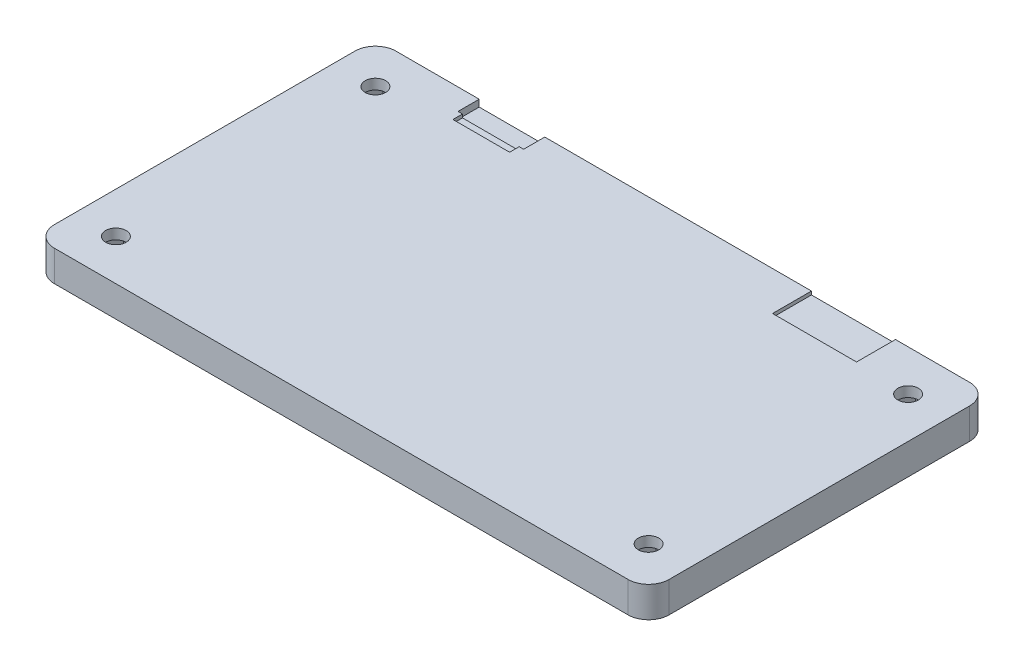
SolidWorks part; units mm, degrees
ref_plane "前视基准面" through (0, 0, 0) normal (0, 0, 1) x (1, 0, 0)
ref_plane "上视基准面" through (0, 0, 0) normal (0, 1, 0) x (1, 0, 0)
ref_plane "右视基准面" through (0, 0, 0) normal (1, 0, 0) x (0, 0, -1)
other "Configuration Table"
sketch "草图1" plane through (0, 0, 0) normal (0, 1, 0) x (1, 0, 0)
  line L1 (-42, -25) -> (42, -25)
  line L2 (-45, -22) -> (-45, 22)
  line L3 (-42, 25) -> (42, 25)
  line L4 (45, -22) -> (45, 22)
  line L5 (-45, -25) -> (45, 25) construction
  line L6 (-45, 25) -> (45, -25) construction
  arc A0 (-42, -25) -> (-45, -22) centre (-42, -22) cw
  arc A1 (45, -22) -> (42, -25) centre (42, -22) cw
  arc A2 (45, 22) -> (42, 25) centre (42, 22) ccw
  arc A3 (-45, 22) -> (-42, 25) centre (-42, 22) cw
  circle A4 centre (-39, 19) radius 1.5
  circle A5 centre (39, 19) radius 1.5
  circle A6 centre (-39, -19) radius 1.5
  circle A7 centre (39, -19) radius 1.5
  point P0 (0, 0)
  dimension "D3" = 3
  dimension "D4" = 3
  dimension "D1" = 90
  dimension "D2" = 50
  dimension "D5" = 6
  dimension "D6" = 6
  dimension "D7" = 6
  dimension "D8" = 6
extrude "凸台-拉伸1" add sketch "草图1" along normal blind 3.5
sketch "草图2" plane through (0, 3.5, 0) normal (0, 1, 0) x (1, 0, 0)
  line L1 (-29.8, 25) -> (-20.2, 25)
  line L2 (-29.8, 25) -> (-29.8, 21.9)
  line L3 (-29.8, 21.9) -> (-20.2, 21.9)
  line L4 (-20.2, 25) -> (-20.2, 21.9)
  line L7 (-29.15, 20.5) -> (-20.85, 20.5)
  line L8 (-29.15, 20.5) -> (-29.15, 21.9)
  line L9 (-29.15, 21.9) -> (-20.85, 21.9)
  line L10 (-20.85, 20.5) -> (-20.85, 21.9)
  line L12 (18.85, 19.3) -> (31.15, 19.3)
  line L13 (18.85, 19.3) -> (18.85, 25)
  line L14 (18.85, 25) -> (31.15, 25)
  line L15 (31.15, 19.3) -> (31.15, 25)
extrude "切除-拉伸1" cut sketch "草图2" against normal blind 0.5 contours L12 L15 L14 L13 | L7 L10 L9 L8
extrude "切除-拉伸2" cut sketch "草图2<3>" against normal blind 1 contours L4 L3 L2 L1
sketch "草图2<3>" plane through (0, 3.5, 0) normal (0, 1, 0) x (1, 0, 0) same geometry as "草图2"
sketch "草图3" plane through (0, 0, 0) normal (0, -1, 0) x (1, 0, 0)
  line L1 (-37.4989, 21.6) -> (-40.5011, 21.6)
  line L2 (-40.5011, 21.6) -> (-42.0022, 19)
  line L3 (-42.0022, 19) -> (-40.5011, 16.4)
  line L4 (-40.5011, 16.4) -> (-37.4989, 16.4)
  line L5 (-37.4989, 16.4) -> (-35.9978, 19)
  line L6 (-35.9978, 19) -> (-37.4989, 21.6)
  line L7 (-37.4989, -16.4) -> (-40.5011, -16.4)
  line L8 (-40.5011, -16.4) -> (-42.0022, -19)
  line L9 (-42.0022, -19) -> (-40.5011, -21.6)
  line L10 (-40.5011, -21.6) -> (-37.4989, -21.6)
  line L11 (-37.4989, -21.6) -> (-35.9978, -19)
  line L12 (-35.9978, -19) -> (-37.4989, -16.4)
  line L13 (40.5011, -16.4) -> (37.4989, -16.4)
  line L14 (37.4989, -16.4) -> (35.9978, -19)
  line L15 (35.9978, -19) -> (37.4989, -21.6)
  line L16 (37.4989, -21.6) -> (40.5011, -21.6)
  line L17 (40.5011, -21.6) -> (42.0022, -19)
  line L18 (42.0022, -19) -> (40.5011, -16.4)
  line L19 (37.4989, 21.6) -> (35.9978, 19)
  line L20 (35.9978, 19) -> (37.4989, 16.4)
  line L21 (37.4989, 16.4) -> (40.5011, 16.4)
  line L22 (40.5011, 16.4) -> (42.0022, 19)
  line L23 (42.0022, 19) -> (40.5011, 21.6)
  line L24 (40.5011, 21.6) -> (37.4989, 21.6)
  circle A0 centre (-39, 19) radius 2.6 construction
  circle A1 centre (-39, -19) radius 2.6 construction
  circle A2 centre (39, -19) radius 2.6 construction
  circle A3 centre (39, 19) radius 2.6 construction
  dimension "D1" = 5.2
extrude "切除-拉伸3" cut sketch "草图3" against normal blind 2
sketch "草图5" plane through (0, 0, 0) normal (0, -1, 0) x (1, 0, 0)
  line L0 (35.9978, 19) -> (37.4989, 16.4) construction
  line L1 (37.4989, 21.6) -> (35.9978, 19) construction
  line L2 (40.5011, 21.6) -> (37.4989, 21.6) construction
  line L3 (42.0022, 19) -> (40.5011, 21.6) construction
  line L4 (-45, 22) -> (-45, -22)
  line L5 (-42, -25) -> (42, -25)
  line L6 (45, -22) -> (45, 22)
  line L7 (42, 25) -> (-42, 25)
  line L8 (-45, 22) -> (-45, -22)
  line L9 (-42, -25) -> (42, -25)
  line L10 (45, -22) -> (45, 22)
  line L11 (42, 25) -> (-42, 25)
  line L12 (40.5011, 16.4) -> (42.0022, 19) construction
  line L13 (37.4989, 16.4) -> (40.5011, 16.4) construction
  line L14 (37.4989, -16.4) -> (35.9978, -19) construction
  line L15 (35.9978, -19) -> (37.4989, -21.6) construction
  line L16 (37.4989, -21.6) -> (40.5011, -21.6) construction
  line L17 (40.5011, -21.6) -> (42.0022, -19) construction
  line L18 (42.0022, -19) -> (40.5011, -16.4) construction
  line L19 (40.5011, -16.4) -> (37.4989, -16.4) construction
  line L20 (-40.5011, -16.4) -> (-42.0022, -19) construction
  line L21 (-42.0022, -19) -> (-40.5011, -21.6) construction
  line L22 (-40.5011, -21.6) -> (-37.4989, -21.6) construction
  line L23 (-37.4989, -21.6) -> (-35.9978, -19) construction
  line L24 (-35.9978, -19) -> (-37.4989, -16.4) construction
  line L25 (-37.4989, -16.4) -> (-40.5011, -16.4) construction
  line L26 (-37.4989, 21.6) -> (-40.5011, 21.6) construction
  line L27 (-35.9978, 19) -> (-37.4989, 21.6) construction
  line L28 (-37.4989, 16.4) -> (-35.9978, 19) construction
  line L29 (-42.0022, 19) -> (-40.5011, 16.4) construction
  line L30 (-40.5011, 21.6) -> (-42.0022, 19) construction
  line L31 (-40.5011, 16.4) -> (-37.4989, 16.4) construction
  line L32 (35.9978, 19) -> (37.4989, 16.4)
  line L33 (37.4989, 21.6) -> (35.9978, 19)
  line L34 (40.5011, 21.6) -> (37.4989, 21.6)
  line L35 (42.0022, 19) -> (40.5011, 21.6)
  line L36 (40.5011, 16.4) -> (42.0022, 19)
  line L37 (37.4989, 16.4) -> (40.5011, 16.4)
  line L38 (37.4989, -16.4) -> (35.9978, -19)
  line L39 (35.9978, -19) -> (37.4989, -21.6)
  line L40 (37.4989, -21.6) -> (40.5011, -21.6)
  line L41 (40.5011, -21.6) -> (42.0022, -19)
  line L42 (42.0022, -19) -> (40.5011, -16.4)
  line L43 (40.5011, -16.4) -> (37.4989, -16.4)
  line L44 (-40.5011, -16.4) -> (-42.0022, -19)
  line L45 (-42.0022, -19) -> (-40.5011, -21.6)
  line L46 (-40.5011, -21.6) -> (-37.4989, -21.6)
  line L47 (-37.4989, -21.6) -> (-35.9978, -19)
  line L48 (-35.9978, -19) -> (-37.4989, -16.4)
  line L49 (-37.4989, -16.4) -> (-40.5011, -16.4)
  line L50 (-37.4989, 21.6) -> (-40.5011, 21.6)
  line L51 (-35.9978, 19) -> (-37.4989, 21.6)
  line L52 (-37.4989, 16.4) -> (-35.9978, 19)
  line L53 (-42.0022, 19) -> (-40.5011, 16.4)
  line L54 (-40.5011, 21.6) -> (-42.0022, 19)
  line L55 (-40.5011, 16.4) -> (-37.4989, 16.4)
  arc A4 (-42, 25) -> (-45, 22) centre (-42, 22) ccw
  arc A5 (-45, -22) -> (-42, -25) centre (-42, -22) ccw
  arc A6 (42, -25) -> (45, -22) centre (42, -22) ccw
  arc A7 (45, 22) -> (42, 25) centre (42, 22) ccw
  arc A8 (-42, 25) -> (-45, 22) centre (-42, 22) ccw
  arc A9 (-45, -22) -> (-42, -25) centre (-42, -22) ccw
  arc A10 (42, -25) -> (45, -22) centre (42, -22) ccw
  arc A11 (45, 22) -> (42, 25) centre (42, 22) ccw
  dimension "D1" = 0
extrude "凸台-拉伸3" add sketch "草图5" along normal blind 1
